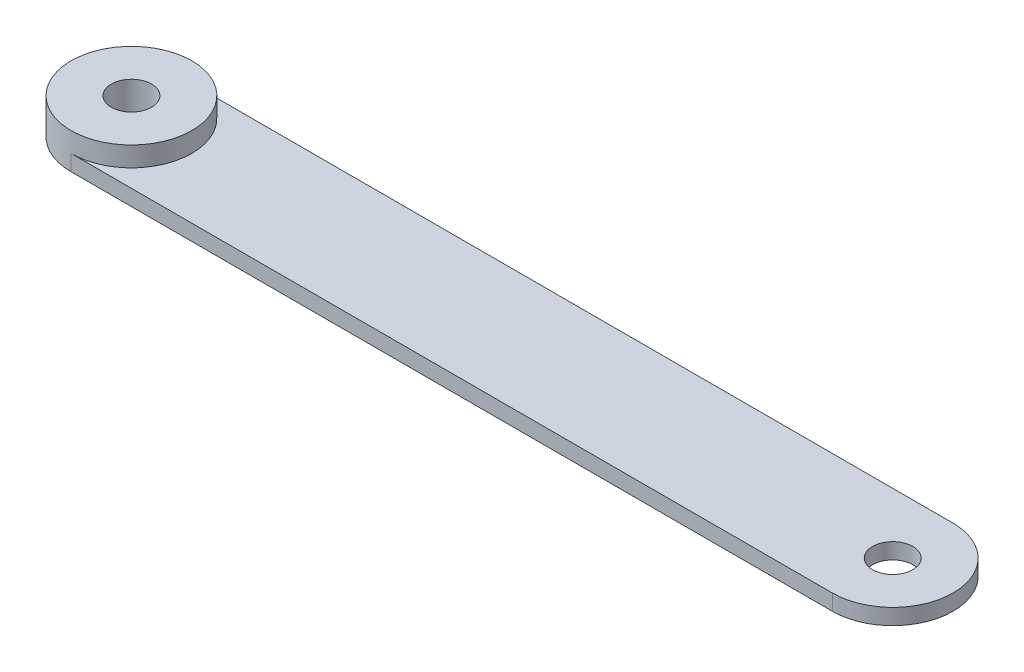
SolidWorks part; units mm, degrees
ref_plane "Front Plane" through (0, 0, 0) normal (0, 0, 1) x (1, 0, 0)
ref_plane "Top Plane" through (0, 0, 0) normal (0, 1, 0) x (1, 0, 0)
ref_plane "Right Plane" through (0, 0, 0) normal (1, 0, 0) x (0, 0, -1)
sketch "Sketch1" [suppressed] plane through (0, 24.1935, 0) normal (0, 1, 0) x (1, 0, 0)
  line L2 (274.193, 24.1935) -> (-274.193, 24.1935)
  line L3 (-274.193, -24.1935) -> (274.193, -24.1935)
  line L4 (274.193, 24.1935) -> (-274.193, 24.1935)
  line L5 (-274.193, -24.1935) -> (274.193, -24.1935)
  circle A0 centre (-274.193, 0) radius 12.7 construction
  circle A1 centre (-274.193, 0) radius 12.7
  arc A2 (274.193, -24.1935) -> (274.193, 24.1935) centre (274.193, 0) ccw
  arc A3 (-274.193, 24.1935) -> (-274.193, -24.1935) centre (-274.193, 0) ccw
  arc A4 (274.193, -24.1935) -> (274.193, 24.1935) centre (274.193, 0) ccw
  arc A5 (-274.193, 24.1935) -> (-274.193, -24.1935) centre (-274.193, 0) ccw
  circle A6 centre (274.193, 0) radius 8.0645 construction
  circle A7 centre (274.193, 0) radius 8.0645
  dimension "D1" = 0
extrude "Boss-Extrude1" [suppressed] add sketch "Sketch1" along normal blind 12.7
sketch "Sketch2" plane through (0, 0, 0) normal (0, 1, 0) x (1, 0, 0)
  line L0 (-152.4, 0) -> (152.4, 0) construction
  line L4 (152.4, 24.1935) -> (-152.4, 24.1935)
  line L5 (-152.4, -24.1935) -> (152.4, -24.1935)
  arc A0 (-155.7904, 23.9548) -> (155.7904, 23.9548) centre (0, -1076.7644) cw
  circle A1 centre (-152.4, 0) radius 8.0645
  arc A2 (-155.7904, -23.9548) -> (155.7904, -23.9548) centre (0, 1076.7644) ccw
  arc A4 (152.4, -24.1935) -> (152.4, 24.1935) centre (152.4, 0) ccw
  arc A5 (-152.4, 24.1935) -> (-152.4, -24.1935) centre (-152.4, 0) ccw
  circle A7 centre (152.4, 0) radius 8.0645
  point P3 (0, 0)
  point P14 (0, 34.925)
  point P18 (0, -34.925)
  dimension "D2" = 16.129
  dimension "D3" = 24.1935
  dimension "D1" = 304.8
  dimension "D4" = 69.85
extrude "Boss-Extrude2" add sketch "Sketch2" along normal mid plane 6.35 separate body contours A5 A2 A4 L5 | A5 L4 A4 A0 | L4 A5 L5 A4 A1 A7 region at (0, 0, 0) region at (0, 0, -28.4876) region at (0, 0, 28.4876)
sketch "Sketch3" plane through (0, 3.175, 0) normal (0, -1, 0) x (1, 0, 0)
  circle A0 centre (-152.4, 0) radius 8.0645 construction
  circle A4 centre (-152.4, 0) radius 8.0645
  circle A5 centre (-152.4, 0) radius 24.1935
  arc A7 (-155.7904, 23.9548) -> (-155.7904, -23.9548) centre (-152.4, 0) ccw construction
extrude "Boss-Extrude3" add sketch "Sketch3" against normal blind 7.9375
sketch "Sketch4" [suppressed] plane through (0, 3.175, 0) normal (0, 1, 0) x (1, 0, 0)
  circle A0 centre (0, 0) radius 3.175
  dimension "D1" = 6.35
extrude "Cut-Extrude1" [suppressed] cut sketch "Sketch4" against normal through all
extrude "Cut-Extrude2" cut sketch "Sketch2<3>" against normal through all both and the other way through all contours A5 A2 A4 L5 | A5 L4 A4 A0 region at (0, 0, -28.4876) region at (0, 0, 28.4876)
sketch "Sketch2<3>" plane through (0, 0, 0) normal (0, 1, 0) x (1, 0, 0) same geometry as "Sketch2"
